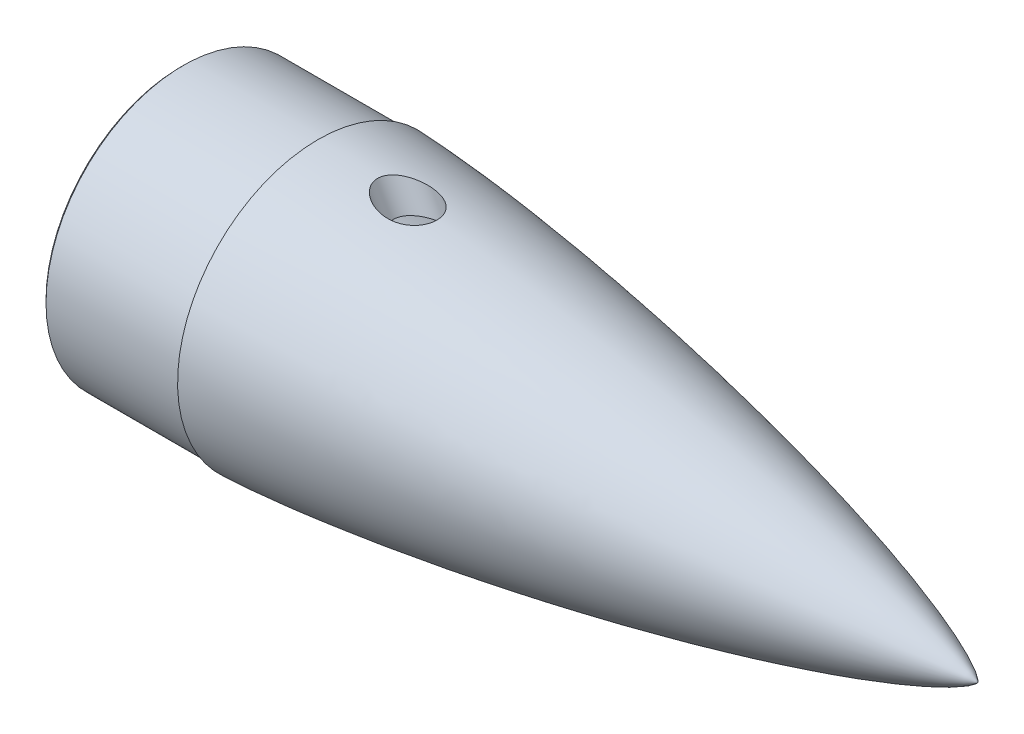
SolidWorks part; units mm, degrees
material "Plain Carbon Steel"
ref_plane "Front Plane" through (0, 0, 0) normal (0, 0, 1) x (1, 0, 0)
ref_plane "Top Plane" through (0, 0, 0) normal (0, 1, 0) x (1, 0, 0)
ref_plane "Right Plane" through (0, 0, 0) normal (1, 0, 0) x (0, 0, -1)
ref_axis "Axis1" through (46.9179, 0, 0) along (-1, 0, 0)
sketch "Sketch10" plane through (0, 0, 0) normal (0, 0, 1) x (1, 0, 0)
  line L1 (-1.0327, 0) -> (486.9547, 0) construction
  line L2 (11.1125, 81.9998) -> (11.1125, 67.4998)
  line L3 (11.1125, 81.9998) -> (-84.6045, 81.9998)
  line L4 (408.9673, 0) -> (368.9673, 0)
  line L5 (-84.6045, 81.9998) -> (-84.6045, 84.9998)
  line L6 (-84.6045, 84.9998) -> (0.3953, 84.9998)
  line L7 (0.3953, 84.9998) -> (0.3953, 86.9998)
  line L8 (11.1125, 67.4998) -> (129.3045, 67.4998)
  line L9 (46.9179, 0) -> (-46.1272, 0) construction
  spline S0 degree 4 poles (408.9673, 0) (408.9649, 0.0135) (408.958, 0.0399) (408.9365, 0.0905) (408.8922, 0.1741) (408.8263, 0.2756) (408.7217, 0.4158) (408.5611, 0.6051) (408.3056, 0.8724) (407.8697, 1.2753) (407.121, 1.8851) (405.8038, 2.8259) (403.4624, 4.2872) (399.3253, 6.5318) (392.4811, 9.7589) (380.6621, 14.628) (363.6372, 20.7117) (342.2152, 27.4765) (317.4285, 34.4976) (291.8793, 41.1048) (266.2105, 47.229) (240.4455, 52.9334) (214.5989, 58.2554) (188.6809, 63.2176) (165.9462, 67.2533) (146.422, 70.4938) (130.1279, 73.0449) (117.0786, 74.9942) (104.0155, 76.8485) (92.5733, 78.3845) (82.7571, 79.6356) (74.5713, 80.6322) (68.0193, 81.4008) (61.4637, 82.1394) (54.9047, 82.8464) (48.3422, 83.5199) (41.7761, 84.1578) (36.0275, 84.6822) (31.0979, 85.1052) (26.9883, 85.4387) (23.6997, 85.6932) (20.0858, 85.9584) (16.7199, 86.189) (13.6021, 86.387) (10.7327, 86.5546) (8.4366, 86.6787) (6.14, 86.7922) (4.1299, 86.8793) (2.4065, 86.9446) (1.2573, 86.979) (0.6827, 86.9949) (0.3953, 86.9998) knots 0 0 0 0 0 0.00013 0.00026 0.00052 0.0009 0.00128 0.001925 0.002882 0.004418 0.006927 0.011111 0.018279 0.030673 0.051704 0.083102 0.139909 0.202703 0.265496 0.32829 0.391083 0.453877 0.516671 0.579464 0.642258 0.673655 0.705051 0.736448 0.767845 0.799242 0.81494 0.830639 0.846337 0.862036 0.877734 0.893432 0.909131 0.924829 0.932678 0.940527 0.948377 0.956226 0.967169 0.972641 0.978113 0.983585 0.989056 0.994528 0.997264 1 1 1 1 1 construction
  spline S1 degree 4 poles (408.9673, 0) (408.9649, 0.0135) (408.958, 0.0399) (408.9365, 0.0905) (408.8922, 0.1741) (408.8263, 0.2756) (408.7217, 0.4158) (408.5611, 0.6051) (408.3056, 0.8724) (407.8697, 1.2753) (407.121, 1.8851) (405.8038, 2.8259) (403.4624, 4.2872) (399.3253, 6.5318) (392.4811, 9.7589) (380.6621, 14.628) (363.6372, 20.7117) (342.2152, 27.4765) (317.4285, 34.4976) (291.8793, 41.1048) (266.2105, 47.229) (240.4455, 52.9334) (214.5989, 58.2554) (188.6809, 63.2176) (165.9462, 67.2533) (146.422, 70.4938) (130.1279, 73.0449) (117.0786, 74.9942) (104.0155, 76.8485) (92.5733, 78.3845) (82.7571, 79.6356) (74.5713, 80.6322) (68.0193, 81.4008) (61.4637, 82.1394) (54.9047, 82.8464) (48.3422, 83.5199) (41.7761, 84.1578) (36.0275, 84.6822) (31.0979, 85.1052) (26.9883, 85.4387) (23.6997, 85.6932) (20.0858, 85.9584) (16.7199, 86.189) (13.6021, 86.387) (10.7327, 86.5546) (8.4366, 86.6787) (6.14, 86.7922) (4.1299, 86.8793) (2.4065, 86.9446) (1.2573, 86.979) (0.6827, 86.9949) (0.3953, 86.9998) knots 0 0 0 0 0 0.00013 0.00026 0.00052 0.0009 0.00128 0.001925 0.002882 0.004418 0.006927 0.011111 0.018279 0.030673 0.051704 0.083102 0.139909 0.202703 0.265496 0.32829 0.391083 0.453877 0.516671 0.579464 0.642258 0.673655 0.705051 0.736448 0.767845 0.799242 0.81494 0.830639 0.846337 0.862036 0.877734 0.893432 0.909131 0.924829 0.932678 0.940527 0.948377 0.956226 0.967169 0.972641 0.978113 0.983585 0.989056 0.994528 0.997264 1 1 1 1 1
  spline S2 degree 4 poles (368.9673, 0) (368.9653, 0.0123) (368.9594, 0.0365) (368.9406, 0.083) (368.9023, 0.1587) (368.8455, 0.2503) (368.7557, 0.3766) (368.6167, 0.5484) (368.3929, 0.7936) (368.0087, 1.1649) (367.3447, 1.7299) (366.1761, 2.6016) (364.0928, 3.96) (360.426, 6.0407) (354.4022, 9.0183) (344.043, 13.5077) (329.152, 19.1285) (310.4252, 25.3986) (288.7413, 31.9337) (266.3785, 38.1061) (243.9014, 43.8469) (221.332, 49.212) (198.684, 54.2345) (175.9669, 58.9343) (156.0346, 62.7717) (138.9133, 65.8645) (124.6221, 68.3077) (113.1754, 70.1797) (101.7151, 71.9664) (91.6754, 73.4517) (83.0615, 74.6659) (75.8775, 75.6363) (70.1269, 76.3867) (64.3728, 77.1101) (58.6152, 77.8049) (52.854, 78.4695) (47.0892, 79.1019) (42.0417, 79.6247) (37.7129, 80.0488) (34.1039, 80.385) (31.2157, 80.6428) (28.0648, 80.911) (24.6507, 81.1843) (21.4654, 81.4195) (18.5093, 81.6177) (16.0448, 81.767) (14.3191, 81.8612) (12.8395, 81.9336) (11.8527, 81.9739) (11.3593, 81.993) (11.1125, 81.9998) knots 0 0 0 0 0 0.000135 0.00027 0.00054 0.00092 0.001299 0.001947 0.002931 0.004512 0.007081 0.01138 0.018708 0.031424 0.052705 0.084103 0.14091 0.203703 0.266497 0.329291 0.392084 0.454878 0.517672 0.580465 0.643259 0.674656 0.706052 0.737449 0.768846 0.800243 0.815941 0.831639 0.847338 0.863036 0.878735 0.894433 0.910132 0.92583 0.933679 0.941528 0.949378 0.957227 0.96792 0.978613 0.98396 0.989307 0.994653 0.997327 1 1 1 1 1 construction
  spline S3 degree 4 poles (368.9673, 0) (368.9653, 0.0123) (368.9594, 0.0365) (368.9406, 0.083) (368.9023, 0.1587) (368.8455, 0.2503) (368.7557, 0.3766) (368.6167, 0.5484) (368.3929, 0.7936) (368.0087, 1.1649) (367.3447, 1.7299) (366.1761, 2.6016) (364.0928, 3.96) (360.426, 6.0407) (354.4022, 9.0183) (344.043, 13.5077) (329.152, 19.1285) (310.4252, 25.3986) (288.7413, 31.9337) (266.3785, 38.1061) (243.9014, 43.8469) (221.332, 49.212) (198.684, 54.2345) (175.9669, 58.9343) (156.0346, 62.7717) (141.5091, 65.3956) (132.6794, 66.9245) (129.5628, 67.4559) (129.3045, 67.4998) knots 0 0 0 0 0 0.000135 0.00027 0.00054 0.00092 0.001299 0.001947 0.002931 0.004512 0.007081 0.01138 0.018708 0.031424 0.052705 0.084103 0.14091 0.203703 0.266497 0.329291 0.392084 0.454878 0.517672 0.580465 0.643259 0.674656 0.677492 0.677492 0.677492 0.677492 0.677492
  dimension "D1" = 86.9998
  dimension "D2" = 3
  dimension "D3" = 410
  dimension "D4" = 84.9998
  dimension "D5" = 370
  dimension "D6" = 84.9998
  dimension "D7" = 19.5
  dimension "D8" = 118.192
revolve "Revolve1" add sketch "Sketch10" angle 360 about axis through (46.9179, 0, 0) along (-1, 0, 0)
chamfer "Chamfer1" distance 1.5 angle 45 1 edges at (-84.6045, 0, -84.9998)
ref_plane "Plane2" through (11.1125, 0, 0) normal (-1, 0, 0) x (0, 0, 1)
sketch "Sketch12" plane through (11.1125, 0, 0) normal (-1, 0, 0) x (0, 0, 1)
  line L0 (-81.9998, 0) -> (-67.4998, 0)
  circle A2 centre (0, 0) radius 81.9998 construction
  circle A3 centre (0, 0) radius 67.4998 construction
  circle A4 centre (-74.7498, 0) radius 4
  circle A5 centre (-37.3749, 64.7353) radius 4
  circle A6 centre (37.3749, 64.7353) radius 4
  circle A7 centre (74.7498, 0) radius 4
  circle A8 centre (37.3749, -64.7353) radius 4
  circle A9 centre (-37.3749, -64.7353) radius 4
  point P17 (-50.2998, -44.6412)
  point P25 (0, 0)
  dimension "D1" = 6
hole_wizard "Tapped Hole for M4x0.7 Helicoil1" positions "Sketch17" profile "Sketch18" tap size "M4x0.7" standard "Helicoil® Metric"
sketch "Sketch17" plane through (11.1125, 0, 0) normal (-1, 0, 0) x (0, 0, 1)
  point P0 (-37.3749, 64.7353)
sketch "Sketch18" plane through (11.1125, 64.7353, -37.3749) normal (0, 1, 0) x (0, 0, 1)
  line L0 (0, 0) -> (0, 31.2618)
  line L1 (0, 31.2618) -> (2.1, 30)
  line L2 (2.1, 30) -> (2.1, 0)
  line L5 (2.1, 0) -> (0, 0)
  line L10 (0, 31.2618) -> (-2.1, 30) construction
  line L11 (0, -6.35) -> (0, 107.95) construction
  dimension "Tap Drill Dia." = 4.2
  dimension "Tap Drill Depth" = 30
  dimension "Drill Angle" = 118
cosmetic thread "Hole Thread3" parameters "D1"=4.7, "D2"=5.007
pattern_circular "CirPattern1" count 6 over 360 about axis through (11.1125, 0, 0) along (1, 0, 0) of "Tapped Hole for M4x0.7 Helicoil1"
ref_plane "Plane3" through (0, 60, 0) normal (0, 1, 0) x (1, 0, 0)
sketch "Sketch20" plane through (0, 60, 0) normal (0, 1, 0) x (1, 0, 0)
  line L0 (46.9179, 0) -> (-46.1272, 0) construction
  line L1 (24.7702, 25) -> (64.7702, 25)
  line L2 (24.7702, 25) -> (24.7702, -15)
  line L3 (24.7702, -15) -> (64.7702, -15)
  line L4 (64.7702, 25) -> (64.7702, -15)
  line L5 (24.7702, 25) -> (64.7702, -15) construction
  line L6 (24.7702, -15) -> (64.7702, 25) construction
  point P4 (44.7702, 5)
  dimension "D1" = 40
  dimension "D2" = 15
  dimension "D3" = 40
extrude "Cut-Extrude3" [suppressed] cut sketch "Sketch20" along normal blind 12
sketch "Sketch22" plane through (0, 60, 0) normal (0, 1, 0) x (1, 0, 0)
  circle A0 centre (32, 6) radius 7.5
  dimension "D1" = 15
extrude "Cut-Extrude4" [suppressed] cut sketch "Sketch22" along normal through all
sketch "Sketch24" plane through (0, 60, 0) normal (0, 1, 0) x (1, 0, 0)
  line L0 (38.1988, 66.2764) -> (38.1988, 16.8548)
ref_plane "Plane4" through (-16.4311, 28.4594, 0) normal (-0.5, 0.866, 0) x (0, 0, 1)
sketch "Sketch26" plane through (-16.4311, 28.4594, 0) normal (-0.5, 0.866, 0) x (0, 0, 1)
  circle A0 centre (0, 89.5256) radius 15
extrude "Cut-Extrude5" cut sketch "Sketch26" against normal blind 50
extrude "Cut-Extrude6" cut sketch "Sketch26<2>" along normal blind 50
sketch "Sketch26<2>" plane through (-16.4311, 28.4594, 0) normal (-0.5, 0.866, 0) x (0, 0, 1) same geometry as "Sketch26"
equation "\"TubeDiameter\" = 6.250in"
